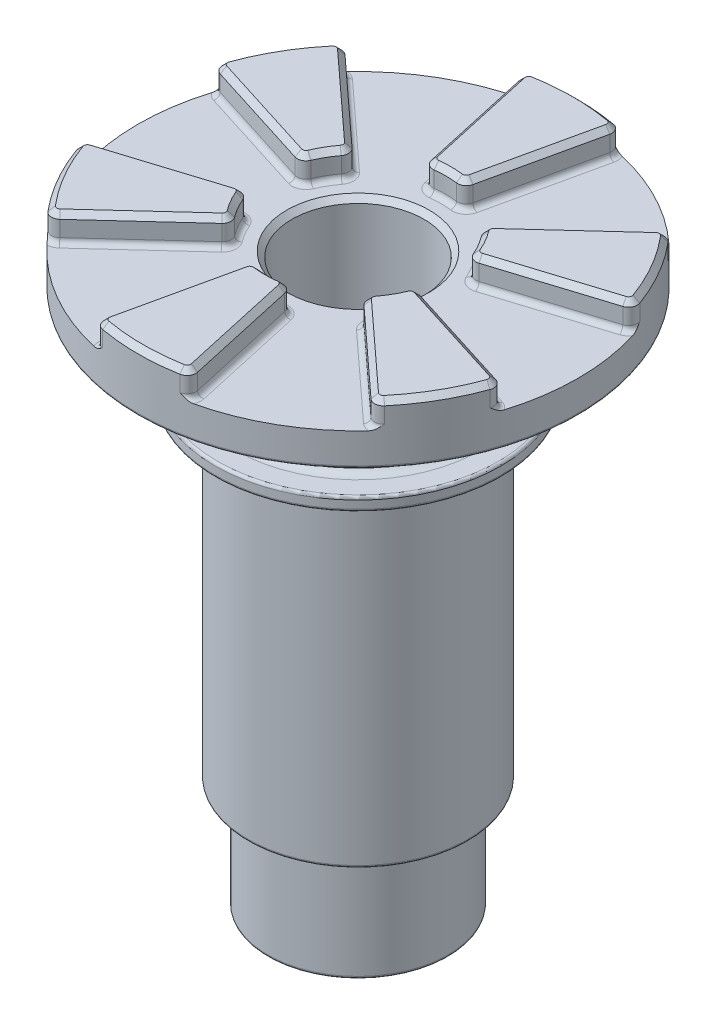
SolidWorks part; units mm, degrees
material "AISI Type S7 Tool Steel"
ref_plane "Front Plane" through (0, 0, 0) normal (0, 0, 1) x (1, 0, 0)
ref_plane "Top Plane" through (0, 0, 0) normal (0, 1, 0) x (1, 0, 0)
ref_plane "Right Plane" through (0, 0, 0) normal (1, 0, 0) x (0, 0, -1)
sketch "Sketch1" plane through (0, 0, 0) normal (0, 0, 1) x (1, 0, 0)
  line L0 (9.525, 81.788) -> (31.75, 81.788)
  line L1 (31.75, 81.788) -> (31.75, 77.0255)
  line L4 (15.875, 65.659) -> (20.6375, 65.659)
  line L5 (20.6375, 65.659) -> (20.6375, 63.754)
  line L6 (20.6375, 63.754) -> (15.875, 63.754)
  line L8 (13.0175, 0) -> (11.7475, 0)
  line L9 (7.9375, 3.81) -> (7.9375, 19.304)
  line L10 (31.75, 77.0255) -> (20.6375, 77.0255)
  line L11 (20.6375, 77.0255) -> (20.6375, 69.088)
  line L12 (20.6375, 69.088) -> (15.875, 69.088)
  line L13 (15.875, 69.088) -> (15.875, 65.659)
  line L14 (0, 0) -> (0, 81.788) construction
  line L15 (11.7475, 0) -> (7.9375, 3.81)
  line L19 (13.0175, 0) -> (13.0175, 15.875)
  line L22 (7.9375, 19.304) -> (9.525, 19.304)
  line L23 (9.525, 19.304) -> (9.525, 81.788)
  line L24 (15.875, 63.754) -> (15.875, 15.875)
  line L25 (15.875, 15.875) -> (13.0175, 15.875)
  point P10 (7.9375, 0)
  dimension "D1" = 7.9375
  dimension "D2" = 81.788
  dimension "D3" = 15.875
  dimension "D4" = 4.7625
  dimension "D5" = 1.905
  dimension "D6" = 31.75
  dimension "D7" = 6.35
  dimension "D8" = 20.6375
  dimension "D9" = 7.9375
  dimension "D10" = 3.429
  dimension "D11" = 5.08
  dimension "D14" = 9.525
  dimension "D15" = 19.304
  dimension "D16" = 15.875
revolve "Revolve1" add sketch "Sketch1" angle 360 about L14
sketch "Sketch2" plane through (0, 0, 0) normal (0, -1, 0) x (1, 0, 0)
  line L12 (-7.9375, 2.986) -> (-7.9375, -2.986)
  line L13 (-6.5547, -5.3811) -> (-1.3828, -8.3671)
  line L14 (1.3828, -8.3671) -> (6.5547, -5.3811)
  line L15 (7.9375, -2.986) -> (7.9375, 2.986)
  line L16 (6.5547, 5.3811) -> (1.3828, 8.3671)
  line L17 (-1.3828, 8.3671) -> (-6.5547, 5.3811)
  circle A21 centre (0, 0) radius 7.9375 construction
  arc A22 (-1.3828, 8.3671) -> (-0.7938, 8.9621) centre (-2.1765, 9.7419) ccw
  arc A23 (-0.7938, 8.9621) -> (0.7937, 8.9621) centre (0, 8.5145) cw
  arc A24 (0.7937, 8.9621) -> (1.3828, 8.3671) centre (2.1765, 9.7419) ccw
  arc A25 (6.5547, 5.3811) -> (7.3646, 5.1685) centre (7.3485, 6.7559) ccw
  arc A26 (7.3646, 5.1685) -> (8.1583, 3.7937) centre (7.3738, 4.2573) cw
  arc A27 (8.1583, 3.7937) -> (7.9375, 2.986) centre (9.525, 2.986) ccw
  arc A28 (7.9375, -2.986) -> (8.1583, -3.7937) centre (9.525, -2.986) ccw
  arc A29 (8.1583, -3.7937) -> (7.3646, -5.1685) centre (7.3738, -4.2573) cw
  arc A30 (7.3646, -5.1685) -> (6.5547, -5.3811) centre (7.3485, -6.7559) ccw
  arc A31 (1.3828, -8.3671) -> (0.7937, -8.9621) centre (2.1765, -9.7419) ccw
  arc A32 (0.7937, -8.9621) -> (-0.7938, -8.9621) centre (0, -8.5145) cw
  arc A33 (-0.7938, -8.9621) -> (-1.3828, -8.3671) centre (-2.1765, -9.7419) ccw
  arc A34 (-6.5547, -5.3811) -> (-7.3646, -5.1685) centre (-7.3485, -6.7559) ccw
  arc A35 (-7.3646, -5.1685) -> (-8.1583, -3.7937) centre (-7.3738, -4.2573) cw
  arc A36 (-8.1583, -3.7937) -> (-7.9375, -2.986) centre (-9.525, -2.986) ccw
  arc A37 (-7.9375, 2.986) -> (-8.1583, 3.7937) centre (-9.525, 2.986) ccw
  arc A38 (-8.1583, 3.7937) -> (-7.3646, 5.1685) centre (-7.3738, 4.2573) cw
  arc A39 (-7.3646, 5.1685) -> (-6.5547, 5.3811) centre (-7.3485, 6.7559) ccw
  circle A40 centre (0, 0) radius 8.5145 construction
  point P17 (0, -9.4258)
  point P18 (0, 9.4258)
  dimension "D2" = 1.5875
  dimension "D4" = 15.875
  dimension "D6" = 0.9113
  dimension "D5" = 17.0291
  dimension "D7" = 18.8516
  dimension "D3" = 1.5875
extrude "Cut-Extrude1" cut sketch "Sketch2" against normal blind 28.575
sketch "Sketch3" plane through (0, 81.788, 0) normal (0, 1, 0) x (1, 0, 0)
  line L0 (6.5914, -29.7317) -> (3.0111, -13.5824)
  line L1 (-6.5914, -29.7317) -> (-3.0111, -13.5824)
  line L8 (0, 0) -> (3.0111, -13.5824) construction
  line L9 (-22.4527, -20.5741) -> (-10.2571, -9.3989)
  line L10 (-29.044, -9.1576) -> (-13.2683, -4.1835)
  line L11 (0, 0) -> (-10.2571, -9.3989) construction
  line L12 (-29.044, 9.1576) -> (-13.2683, 4.1835)
  line L13 (-22.4527, 20.5741) -> (-10.2571, 9.3989)
  line L14 (0, 0) -> (-13.2683, 4.1835) construction
  line L15 (-6.5914, 29.7317) -> (-3.0111, 13.5824)
  line L16 (6.5914, 29.7317) -> (3.0111, 13.5824)
  line L17 (0, 0) -> (-3.0111, 13.5824) construction
  line L18 (22.4527, 20.5741) -> (10.2571, 9.3989)
  line L19 (29.044, 9.1576) -> (13.2683, 4.1835)
  line L20 (0, 0) -> (10.2571, 9.3989) construction
  line L21 (29.044, -9.1576) -> (13.2683, -4.1835)
  line L22 (22.4527, -20.5741) -> (10.2571, -9.3989)
  line L23 (0, 0) -> (13.2683, -4.1835) construction
  line L24 (0, 0) -> (-1.6102, -12.5975) construction
  arc A0 (-5.5744, -31.2568) -> (5.5744, -31.2568) centre (0, 0) ccw
  arc A1 (-1.6102, -12.5975) -> (1.6102, -12.5975) centre (0, 0) ccw
  arc A2 (-5.5744, -31.2568) -> (-6.5914, -29.7317) centre (-5.3515, -30.0065) cw
  arc A3 (-3.0111, -13.5824) -> (-1.6102, -12.5975) centre (-1.7712, -13.8573) cw
  arc A4 (1.6102, -12.5975) -> (3.0111, -13.5824) centre (1.7712, -13.8573) cw
  arc A5 (6.5914, -29.7317) -> (5.5744, -31.2568) centre (5.3515, -30.0065) cw
  circle A6 centre (0, 0) radius 31.75 construction
  arc A25 (-29.8564, -10.8008) -> (-24.282, -20.456) centre (0, 0) ccw
  arc A26 (-11.7149, -4.9043) -> (-10.1046, -7.6932) centre (0, 0) ccw
  arc A27 (-29.8564, -10.8008) -> (-29.044, -9.1576) centre (-28.6622, -10.3688) cw
  arc A28 (-13.2683, -4.1835) -> (-11.7149, -4.9043) centre (-12.8864, -5.3947) cw
  arc A29 (-10.1046, -7.6932) -> (-10.2571, -9.3989) centre (-11.1151, -8.4626) cw
  arc A30 (-22.4527, -20.5741) -> (-24.282, -20.456) centre (-23.3107, -19.6378) cw
  arc A31 (-24.282, 20.456) -> (-29.8564, 10.8008) centre (0, 0) ccw
  arc A32 (-10.1046, 7.6932) -> (-11.7149, 4.9043) centre (0, 0) ccw
  arc A33 (-24.282, 20.456) -> (-22.4527, 20.5741) centre (-23.3107, 19.6378) cw
  arc A34 (-10.2571, 9.3989) -> (-10.1046, 7.6932) centre (-11.1151, 8.4626) cw
  arc A35 (-11.7149, 4.9043) -> (-13.2683, 4.1835) centre (-12.8864, 5.3947) cw
  arc A36 (-29.044, 9.1576) -> (-29.8564, 10.8008) centre (-28.6622, 10.3688) cw
  arc A37 (5.5744, 31.2568) -> (-5.5744, 31.2568) centre (0, 0) ccw
  arc A38 (1.6102, 12.5975) -> (-1.6102, 12.5975) centre (0, 0) ccw
  arc A39 (5.5744, 31.2568) -> (6.5914, 29.7317) centre (5.3515, 30.0065) cw
  arc A40 (3.0111, 13.5824) -> (1.6102, 12.5975) centre (1.7712, 13.8573) cw
  arc A41 (-1.6102, 12.5975) -> (-3.0111, 13.5824) centre (-1.7712, 13.8573) cw
  arc A42 (-6.5914, 29.7317) -> (-5.5744, 31.2568) centre (-5.3515, 30.0065) cw
  arc A43 (29.8564, 10.8008) -> (24.282, 20.456) centre (0, 0) ccw
  arc A44 (11.7149, 4.9043) -> (10.1046, 7.6932) centre (0, 0) ccw
  arc A45 (29.8564, 10.8008) -> (29.044, 9.1576) centre (28.6622, 10.3688) cw
  arc A46 (13.2683, 4.1835) -> (11.7149, 4.9043) centre (12.8864, 5.3947) cw
  arc A47 (10.1046, 7.6932) -> (10.2571, 9.3989) centre (11.1151, 8.4626) cw
  arc A48 (22.4527, 20.5741) -> (24.282, 20.456) centre (23.3107, 19.6378) cw
  arc A49 (24.282, -20.456) -> (29.8564, -10.8008) centre (0, 0) ccw
  arc A50 (10.1046, -7.6932) -> (11.7149, -4.9043) centre (0, 0) ccw
  arc A51 (24.282, -20.456) -> (22.4527, -20.5741) centre (23.3107, -19.6378) cw
  arc A52 (10.2571, -9.3989) -> (10.1046, -7.6932) centre (11.1151, -8.4626) cw
  arc A53 (11.7149, -4.9043) -> (13.2683, -4.1835) centre (12.8864, -5.3947) cw
  arc A54 (29.044, -9.1576) -> (29.8564, -10.8008) centre (28.6622, -10.3688) cw
  point P10 (-6.872, -30.9974)
  point P13 (-2.7488, -12.399)
  point P16 (2.7488, -12.399)
  point P19 (6.872, -30.9974)
  dimension "D1" = 12.7
  dimension "D2" = 1.27
  dimension "D3" = 25
  dimension "D4" = 6
extrude "Boss-Extrude1" add sketch "Sketch3" along normal blind 3.81
chamfer "Chamfer2" distance 0.762 angle 45 49 edges at (-4.8012, 85.598, 21.657) (-6.4081, 85.598, 30.7111) (-2.5016, 85.598, 12.8183) (0, 85.598, 31.75) (0, 85.598, 12.7) (6.4081, 85.598, 30.7111) (2.5016, 85.598, 12.8183) (4.8012, 85.598, 21.657) (0, 81.788, -9.525) (4.8012, 85.598, -21.657) (6.4081, 85.598, -30.7111) (2.5016, 85.598, -12.8183) (0, 85.598, -31.75) (0, 85.598, -12.7) (-6.4081, 85.598, -30.7111) (-2.5016, 85.598, -12.8183) (-4.8012, 85.598, -21.657) (-16.3549, 85.598, -14.9865) (-23.3925, 85.598, -20.9051) (-9.8502, 85.598, -8.5756) (-27.4963, 85.598, -15.875) (-10.9985, 85.598, -6.35) (-29.8006, 85.598, -9.806) (-12.3518, 85.598, -4.2427) (-21.1562, 85.598, -6.6705) (-16.3549, 85.598, 14.9865) (-9.8502, 85.598, 8.5756) (-23.3925, 85.598, 20.9051) (-10.9985, 85.598, 6.35) (-27.4963, 85.598, 15.875) (-12.3518, 85.598, 4.2427) (-29.8006, 85.598, 9.806) (-21.1562, 85.598, 6.6705) (16.3549, 85.598, -14.9865) (9.8502, 85.598, -8.5756) (23.3925, 85.598, -20.9051) (10.9985, 85.598, -6.35) (27.4963, 85.598, -15.875) (12.3518, 85.598, -4.2427) (29.8006, 85.598, -9.806) (21.1562, 85.598, -6.6705) (21.1562, 85.598, 6.6705) (12.3518, 85.598, 4.2427) (29.8006, 85.598, 9.806) (10.9985, 85.598, 6.35) (27.4963, 85.598, 15.875) (9.8502, 85.598, 8.5756) (23.3925, 85.598, 20.9051) (16.3549, 85.598, 14.9865)
fillet "Fillet1" radius 0.762 42 edges at (6.4081, 81.788, 30.7111) (4.8012, 81.788, 21.657) (2.5016, 81.788, 12.8183) (-6.4081, 81.788, 30.7111) (-4.8012, 81.788, 21.657) (-2.5016, 81.788, 12.8183) (0, 81.788, 12.7) (29.8006, 81.788, 9.806) (23.3925, 81.788, 20.9051) (16.3549, 81.788, 14.9865) (9.8502, 81.788, 8.5756) (10.9985, 81.788, 6.35) (12.3518, 81.788, 4.2427) (23.3925, 81.788, -20.9051) (29.8006, 81.788, -9.806) (21.1562, 81.788, -6.6705) (12.3518, 81.788, -4.2427) (10.9985, 81.788, -6.35) (9.8502, 81.788, -8.5756) (-6.4081, 81.788, -30.7111) (6.4081, 81.788, -30.7111) (4.8012, 81.788, -21.657) (2.5016, 81.788, -12.8183) (0, 81.788, -12.7) (-2.5016, 81.788, -12.8183) (-29.8006, 81.788, -9.806) (-21.1562, 81.788, -6.6705) (-12.3518, 81.788, -4.2427) (-10.9985, 81.788, -6.35) (-9.8502, 81.788, -8.5756) (-23.3925, 81.788, -20.9051) (-23.3925, 81.788, 20.9051) (-16.3549, 81.788, 14.9865) (-9.8502, 81.788, 8.5756) (-10.9985, 81.788, 6.35) (-12.3518, 81.788, 4.2427) (-29.8006, 81.788, 9.806) (21.1562, 81.788, 6.6705) (16.3549, 81.788, -14.9865) (-4.8012, 81.788, -21.657) (-16.3549, 81.788, -14.9865) (-21.1562, 81.788, 6.6705)
fillet "Fillet2" radius 1.905 3 edges at (0, 77.0255, -20.6375) (0, 19.304, -9.525) (0, 63.754, -15.875)
fillet "Fillet4" [suppressed] radius 0.127
fillet "Fillet5" radius 0.381 6 edges at (0, 63.754, -20.6375) (0, 65.659, -20.6375) (0, 69.088, -20.6375) (0, 77.0255, -31.75) (0, 0, -13.0175) (0, 15.875, -15.875)
fillet "Fillet6" [suppressed] radius 0.381
fillet "Fillet7" radius 1.7145 2 edges at (0, 65.659, -15.875) (0, 69.088, -15.875)
fillet "Fillet8" radius 0.635 1 edges at (0, 15.875, -13.0175)
